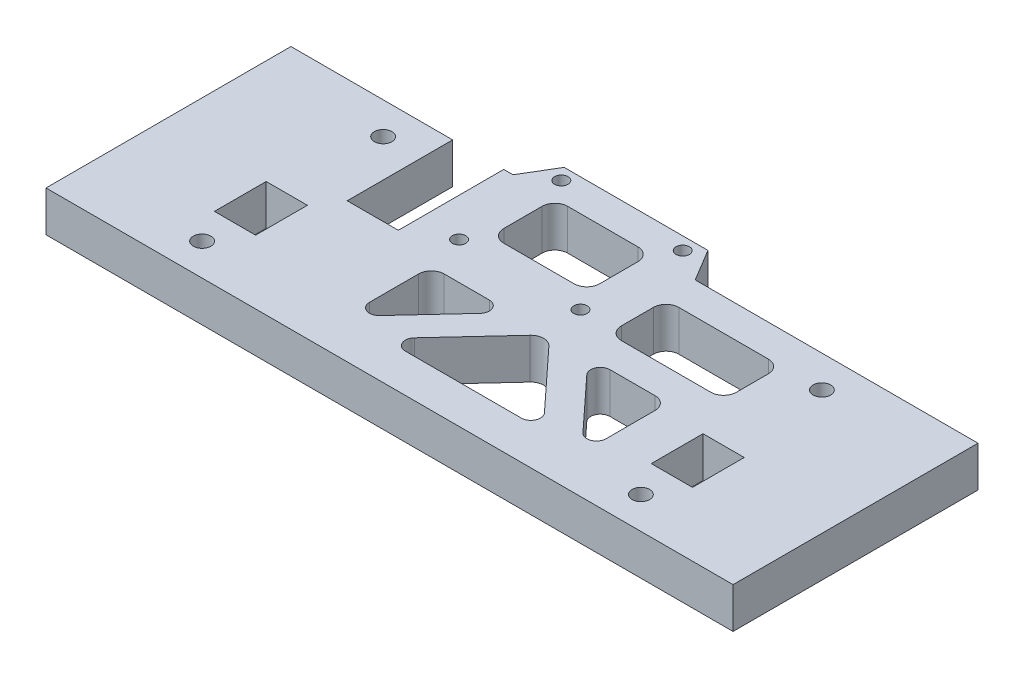
SolidWorks part; units mm, degrees
material "6061 Alloy"
ref_plane "Front Plane" through (0, 0, 0) normal (0, 0, 1) x (1, 0, 0)
ref_plane "Top Plane" through (0, 0, 0) normal (0, 1, 0) x (1, 0, 0)
ref_plane "Right Plane" through (0, 0, 0) normal (1, 0, 0) x (0, 0, -1)
sketch "Sketch1" plane through (0, 0, 0) normal (0, 1, 0) x (1, 0, 0)
  line L0 (107.5, 76.65) -> (107.5, 0) construction
  line L1 (0, 0) -> (215, 0)
  line L2 (0, 0) -> (0, 76.65)
  line L4 (215, 0) -> (215, 76.65)
  line L5 (32.7, 36.2) -> (45.6, 36.2)
  line L6 (32.7, 36.2) -> (32.7, 20)
  line L7 (32.7, 20) -> (45.6, 20)
  line L8 (45.6, 36.2) -> (45.6, 20)
  line L9 (182.3, 20) -> (169.4, 20)
  line L10 (169.4, 36.2) -> (169.4, 20)
  line L11 (182.3, 36.2) -> (169.4, 36.2)
  line L12 (182.3, 36.2) -> (182.3, 20)
  line L13 (0, 76.65) -> (69.5, 76.65)
  line L14 (69.5, 76.65) -> (75.5, 86.65)
  line L15 (75.5, 86.65) -> (120.5, 86.65)
  line L16 (120.5, 86.65) -> (126.5, 76.65)
  line L17 (126.5, 76.65) -> (215, 76.65)
  line L18 (32.7, 28.1) -> (45.6, 28.1) construction
  circle A0 centre (38.85, 66.65) radius 2.75
  circle A5 centre (38.85, 10) radius 2.75
  circle A6 centre (176.15, 66.65) radius 2.75
  circle A7 centre (176.15, 10) radius 2.75
  dimension "D12" = 5.5
  dimension "D16" = 5.5
  dimension "D1" = 215
  dimension "D2" = 76.65
  dimension "D3" = 20
  dimension "D5" = 61.9
  dimension "D6" = 12.9
  dimension "D4" = 10
  dimension "D7" = 6
  dimension "D8" = 38
  dimension "D9" = 76.65
  dimension "D10" = 45
  dimension "D11" = 16.2
  dimension "D14" = 6
  dimension "D13" = 10
  dimension "D15" = 10
extrude "Boss-Extrude1" add sketch "Sketch1" along normal blind 12.7
sketch "Sketch2" plane through (0, 12.7, 0) normal (0, 1, 0) x (1, 0, 0)
  line L1 (50.6, 85.2461) -> (66.6, 85.2461)
  line L2 (50.6, 85.2461) -> (50.6, 43.65)
  line L3 (50.6, 43.65) -> (66.6, 43.65)
  line L4 (66.6, 85.2461) -> (66.6, 43.65)
  line L5 (45.6, 20) -> (45.6, 36.2) construction
  line L12 (69.5, 76.65) -> (0, 76.65) construction
  dimension "D1" = 5
  dimension "D2" = 16
  dimension "D3" = 33
extrude "Cut-Extrude1" cut sketch "Sketch2" against normal through all
sketch "Sketch3" plane through (0, 12.7, 0) normal (0, 1, 0) x (1, 0, 0)
  line L1 (66.6, 43.65) -> (66.6, 76.65) construction
  line L2 (120.5, 86.65) -> (75.5, 86.65) construction
  circle A0 centre (78.6, 82.65) radius 2.1
  circle A1 centre (78.6, 50.65) radius 2.1
  circle A2 centre (116.6, 82.65) radius 2.1
  circle A3 centre (116.6, 50.65) radius 2.1
  dimension "D2" = 4.2
  dimension "D5" = 4.2
  dimension "D8" = 32
  dimension "D1" = 4
  dimension "D3" = 12
  dimension "D4" = 32
  dimension "D7" = 38
  dimension "D6" = 2
extrude "Cut-Extrude2" cut sketch "Sketch3" against normal through all
sketch "Sketch5" plane through (0, 12.7, 0) normal (0, 1, 0) x (1, 0, 0)
  line L2 (86.8013, 17.6174) -> (101.935, 33.9618)
  line L3 (99.7337, 39) -> (85.6, 39)
  line L8 (81.6, 35) -> (81.6, 19.6556)
  line L11 (0, 0) -> (215, 0) construction
  line L12 (66.6, 43.65) -> (66.6, 76.65) construction
  line L13 (115.665, 35.8302) -> (98.265, 17.0382)
  line L14 (118.6, 39) -> (118.6, 12) construction
  line L15 (100.4663, 12) -> (136.7337, 12)
  line L16 (121.535, 35.8302) -> (138.935, 17.0382)
  line L17 (137.4663, 39) -> (151.6, 39)
  line L18 (150.3987, 17.6174) -> (135.265, 33.9618)
  line L19 (155.6, 35) -> (155.6, 19.6556)
  line L20 (120.5, 86.65) -> (75.5, 86.65) construction
  line L21 (86.6, 76.65) -> (108.6, 76.65)
  line L22 (82.6, 72.65) -> (82.6, 60.65)
  line L23 (86.6, 56.65) -> (108.6, 56.65)
  line L24 (112.6, 72.65) -> (112.6, 60.65)
  line L25 (215, 76.65) -> (126.5, 76.65) construction
  line L26 (131.4, 66.65) -> (159.4, 66.65)
  line L27 (127.4, 62.65) -> (127.4, 52.65)
  line L28 (131.4, 48.65) -> (159.4, 48.65)
  line L29 (163.4, 62.65) -> (163.4, 52.65)
  line L30 (169.4, 36.2) -> (169.4, 20) construction
  arc A0 (121.535, 35.8302) -> (115.665, 35.8302) centre (118.6, 33.1125) ccw
  arc A1 (155.6, 35) -> (151.6, 39) centre (151.6, 35) ccw
  arc A2 (81.6, 35) -> (85.6, 39) centre (85.6, 35) cw
  arc A3 (112.6, 72.65) -> (108.6, 76.65) centre (108.6, 72.65) ccw
  arc A4 (108.6, 56.65) -> (112.6, 60.65) centre (108.6, 60.65) ccw
  arc A5 (82.6, 60.65) -> (86.6, 56.65) centre (86.6, 60.65) ccw
  arc A6 (82.6, 72.65) -> (86.6, 76.65) centre (86.6, 72.65) cw
  arc A7 (150.3987, 17.6174) -> (155.6, 19.6556) centre (152.6, 19.6556) ccw
  arc A8 (135.265, 33.9618) -> (137.4663, 39) centre (137.4663, 36) cw
  arc A9 (86.8013, 17.6174) -> (81.6, 19.6556) centre (84.6, 19.6556) cw
  arc A10 (136.7337, 12) -> (138.935, 17.0382) centre (136.7337, 15) ccw
  arc A11 (100.4663, 12) -> (98.265, 17.0382) centre (100.4663, 15) cw
  arc A12 (101.935, 33.9618) -> (99.7337, 39) centre (99.7337, 36) ccw
  arc A13 (163.4, 62.65) -> (159.4, 66.65) centre (159.4, 62.65) ccw
  arc A14 (159.4, 48.65) -> (163.4, 52.65) centre (159.4, 52.65) ccw
  arc A15 (127.4, 52.65) -> (131.4, 48.65) centre (131.4, 52.65) ccw
  arc A16 (127.4, 62.65) -> (131.4, 66.65) centre (131.4, 62.65) cw
  point P25 (155.6, 39)
  point P28 (81.6, 39)
  point P33 (112.6, 56.65)
  point P36 (82.6, 56.65)
  point P39 (82.6, 76.65)
  point P42 (155.6, 12)
  point P45 (130.6, 39)
  point P48 (81.6, 12)
  point P51 (143.6, 12)
  point P54 (93.6, 12)
  point P57 (106.6, 39)
  point P68 (163.4, 66.65)
  point P71 (163.4, 48.65)
  point P76 (127.4, 66.65)
  dimension "D11" = 4
  dimension "D12" = 3
  dimension "D13" = 3
  dimension "D14" = 3
  dimension "D19" = 4
  dimension "D1" = 12
  dimension "D2" = 27
  dimension "D3" = 12
  dimension "D4" = 15
  dimension "D5" = 25
  dimension "D6" = 25
  dimension "D7" = 10
  dimension "D8" = 16
  dimension "D9" = 20
  dimension "D10" = 30
  dimension "D15" = 10
  dimension "D16" = 18
  dimension "D17" = 6
  dimension "D18" = 36
extrude "Cut-Extrude3" cut sketch "Sketch5" against normal through all
equation "\"DriveMotorLength\"= 90mm"
equation "\"DriveMotorGap\"= 10mm"
equation "\"AluminumThickness\"= 0.5in"
equation "\"ChassisWidth\"= ( \"DriveMotorLength\" + \"AluminumThickness\" ) * 2 + \"DriveMotorGap\""
equation "\"RepeatMagnumHoleWidth\"= 19.05mm"
equation "\"MortiseWidth\"= 16mm"
equation "\"ChassisScrewThruHole\"= 5.5mm"
equation "\"D11@Sketch1\"=\"MortiseSlotWidth\""
equation "\"D12@Sketch1\"=\"ChassisScrewThruHole\""
equation "\"D16@Sketch1\"=\"ChassisScrewThruHole\""
equation "\"MortiseSlotWidth\"= 16.2mm"
